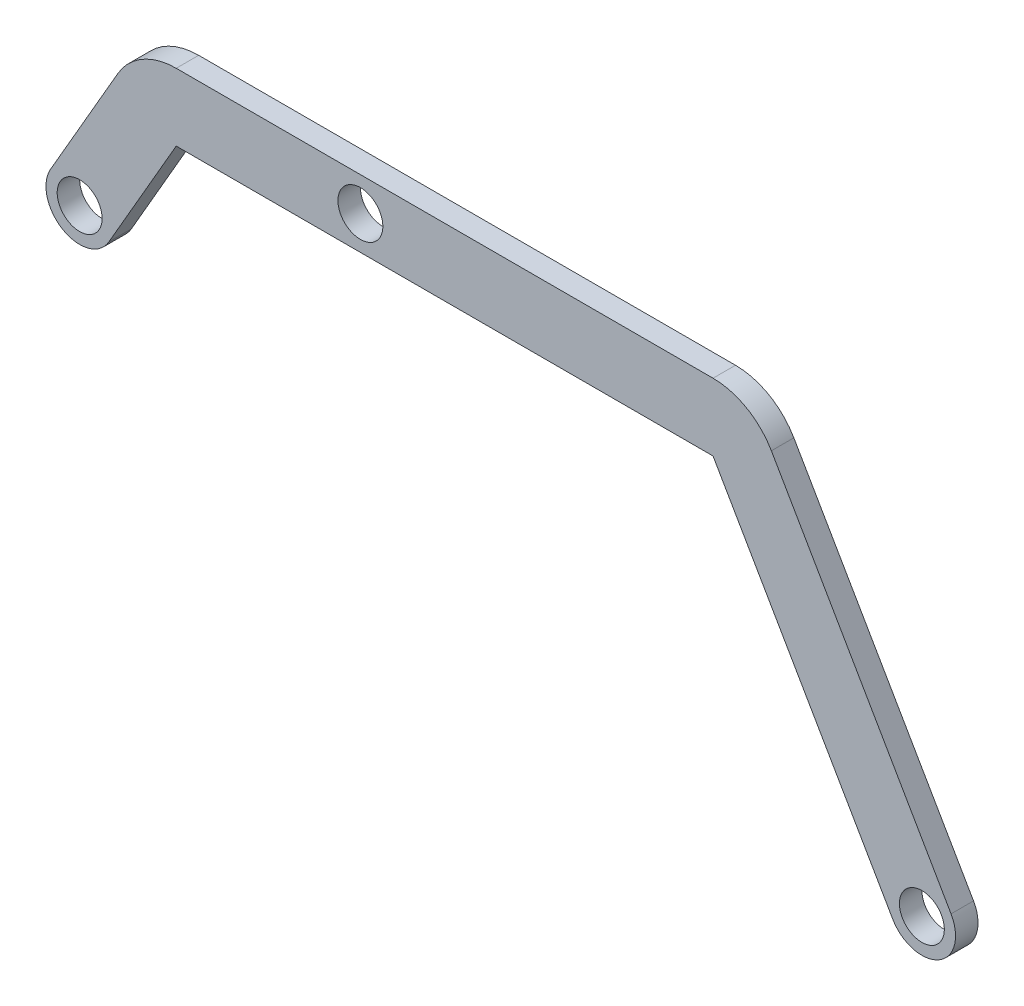
SolidWorks part; units mm, degrees
ref_plane "Front Plane" through (0, 0, 0) normal (0, 0, 1) x (1, 0, 0)
ref_plane "Top Plane" through (0, 0, 0) normal (0, 1, 0) x (1, 0, 0)
ref_plane "Right Plane" through (0, 0, 0) normal (1, 0, 0) x (0, 0, -1)
sketch "Sketch1" plane through (0, 0, 0) normal (0, 0, 1) x (1, 0, 0)
  line L0 (0, -15) -> (0, 15) construction
  line L4 (-82.0096, -15) -> (-112.0096, -66.9615)
  line L6 (-137.9904, -51.9615) -> (-107.9904, 0)
  line L7 (262.9904, -138.5641) -> (182.9904, 0)
  line L9 (157.0096, -15) -> (237.0096, -153.5641)
  line L10 (0, 15) -> (157.0096, 15)
  line L11 (0, -15) -> (157.0096, -15)
  line L12 (0, 15) -> (-82.0096, 15)
  line L13 (0, -15) -> (-82.0096, -15)
  line L14 (237.0096, -153.5641) -> (262.9904, -138.5641) construction
  line L15 (-137.9904, -51.9615) -> (-112.0096, -66.9615) construction
  arc A1 (-107.9904, 0) -> (-82.0096, 15) centre (-82.0096, -15) cw
  arc A2 (182.9904, 0) -> (157.0096, 15) centre (157.0096, -15) ccw
  arc A6 (237.0096, -153.5641) -> (262.9904, -138.5641) centre (250, -146.0641) ccw
  arc A7 (-137.9904, -51.9615) -> (-112.0096, -66.9615) centre (-125, -59.4615) ccw
  point P4 (0, 0)
  point P7 (0, -15)
  point P20 (0, 15)
  dimension "D2" = 60
  dimension "D1" = 30
  dimension "D3" = 250
  dimension "D4" = 160
  dimension "D5" = 125
extrude "Boss-Extrude1" add sketch "Sketch1" along normal blind 10
sketch "Sketch2" plane through (0, 0, 10) normal (0, 0, 1) x (1, 0, 0)
  circle A0 centre (-125, -59.4615) radius 10
  circle A1 centre (250, -146.0641) radius 10
  circle A2 centre (0, 0) radius 10
  dimension "D1" = 20
extrude "Cut-Extrude1" cut sketch "Sketch2" against normal up to surface (10 mm away) up to face at (47.5, -43.007, 0)
